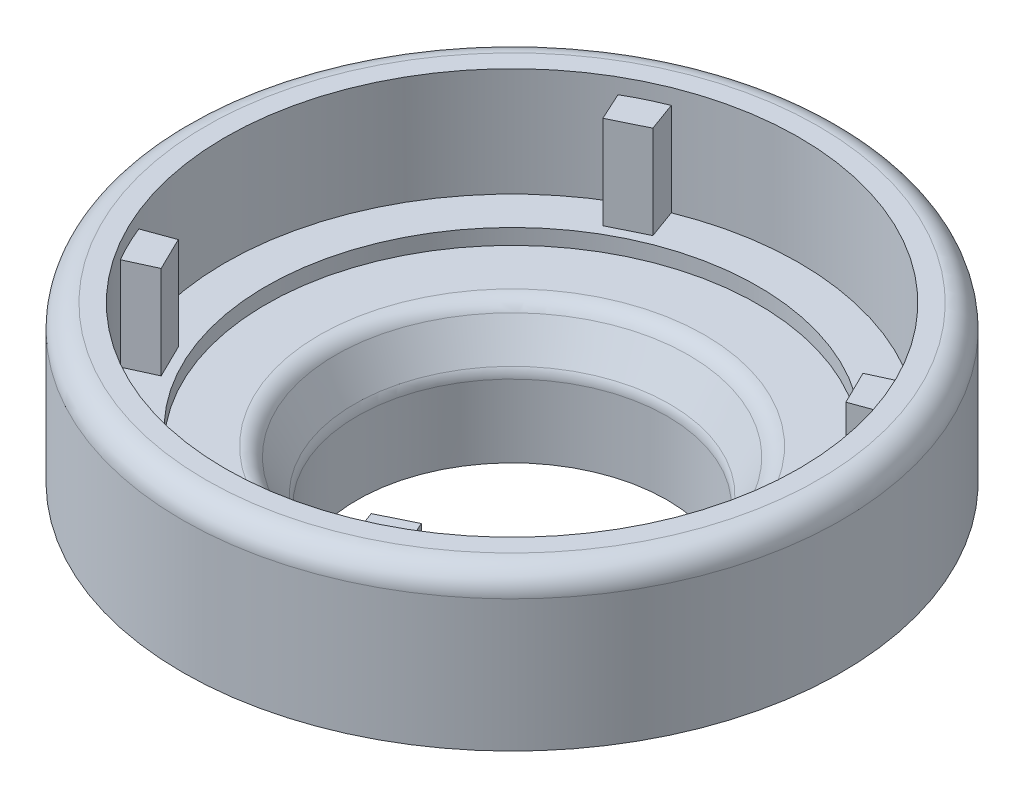
SolidWorks part; units mm, degrees
ref_plane "Front Plane" through (0, 0, 0) normal (0, 0, 1) x (1, 0, 0)
ref_plane "Top Plane" through (0, 0, 0) normal (0, 1, 0) x (1, 0, 0)
ref_plane "Right Plane" through (0, 0, 0) normal (1, 0, 0) x (0, 0, -1)
sketch "Sketch1" plane through (0, 0, 0) normal (0, 1, 0) x (1, 0, 0)
  circle A0 centre (0, 0) radius 12
extrude "Boss-Extrude1" add sketch "Sketch1" along normal blind 5
sketch "Sketch2" plane through (0, 5, 0) normal (0, 1, 0) x (1, 0, 0)
  circle A0 centre (0, 0) radius 12.5
extrude "Boss-Extrude2" add sketch "Sketch2" along normal blind 1
sketch "Sketch6" plane through (0, 6, 0) normal (0, 1, 0) x (1, 0, 0)
  circle A0 centre (0, 0) radius 18.5
  circle A1 centre (0, 0) radius 21.25
  circle M3 centre (0, 0) radius 12.5
extrude "Boss-Extrude7" add sketch "Sketch6" along normal blind 3 contours M3 | A0 M3 | A1 A0 | A1 region at (-17.9767, 6, 0) region at (-20.649, 6, 0) region at (0, 6, 0)
extrude "Boss-Extrude8" add sketch "Sketch6<3>" along normal blind 10
sketch "Sketch6<3>" plane through (0, 6, 0) normal (0, 1, 0) x (1, 0, 0) same geometry as "Sketch6"
sketch "Sketch7" plane through (0, 0, 0) normal (0, -1, 0) x (1, 0, 0)
  circle A0 centre (0, 0) radius 10
extrude "Cut-Extrude2" cut sketch "Sketch7" against normal through all both and the other way through all
sketch "Sketch8" plane through (0, 9, 0) normal (0, 1, 0) x (1, 0, 0)
  line L0 (17.165, 6.9001) -> (15.3007, 6.2219)
  line L1 (15.3007, 6.2219) -> (14.2394, 8.3865)
  line L2 (14.2394, 8.3865) -> (16.0431, 9.2124)
  circle A0 centre (0, 0) radius 18.5 construction
  circle A1 centre (0, 0) radius 18.5 construction
  arc A2 (16.0431, 9.2124) -> (17.165, 6.9001) centre (2.9326, 1.4229) cw
  dimension "D1" = 2.57
extrude "Boss-Extrude9" add sketch "Sketch8" along normal offset from surface (6 mm away) 1 up to face at (0, 16, 21.25)
sketch "Sketch9" plane through (0, 0, 0) normal (0, 0, 1) x (1, 0, 0)
  line L0 (0, 0) -> (0, 14.8885) construction
pattern_circular "CirPattern1" count 4 every 90 about axis through (0, 0, 0) along (0, 1, 0) of "Boss-Extrude9"
sketch "Sketch10" plane through (0, 9, 0) normal (0, 1, 0) x (1, 0, 0)
  circle A0 centre (0, 0) radius 15.8624
extrude "Cut-Extrude3" cut sketch "Sketch10" against normal blind 1
chamfer "Chamfer1" distance 3 angle 30 1 edges at (0, 8, 10) first distance on face at (0, 0, 10)
chamfer "Chamfer2" distance 0.7 angle 64 1 edges at (0, 6, 12.5) first distance on face at (0, 6, 12.5)
fillet "Fillet1" radius 1.2 2 edges at (0, 5, 10) (0, 8, 11.7321)
fillet "Fillet2" radius 1.5 1 edges at (0, 16, 21.25)
